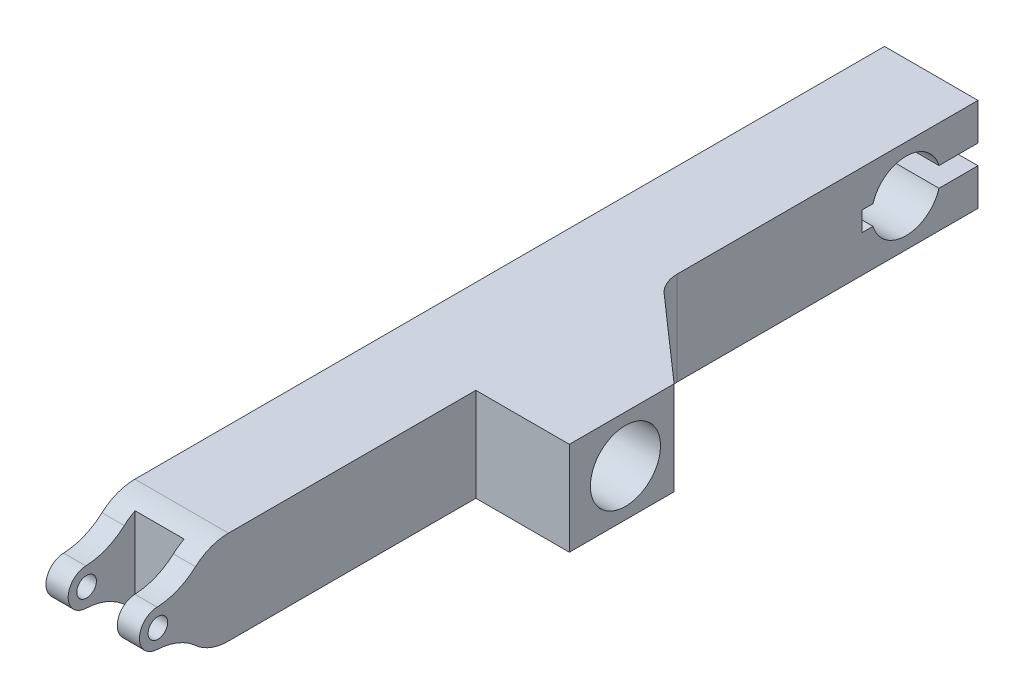
SolidWorks part; units mm, degrees
material "6061-T6 (SS)"
ref_plane "Front Plane" through (0, 0, 0) normal (0, 0, 1) x (1, 0, 0)
ref_plane "Top Plane" through (0, 0, 0) normal (0, 1, 0) x (1, 0, 0)
ref_plane "Right Plane" through (0, 0, 0) normal (1, 0, 0) x (0, 0, -1)
sketch "Sketch1" plane through (0, 0, 0) normal (1, 0, 0) x (0, 0, -1)
  line L0 (0, 0) -> (29.3372, 0) construction
  line L1 (29.3372, -19.05) -> (-175.2557, -19.05)
  line L2 (29.3372, -19.05) -> (29.3372, -4)
  line L3 (29.3372, 19.05) -> (-175.2557, 19.05)
  line L4 (-175.2557, -19.05) -> (-175.2557, 19.05)
  line L5 (-18.025, 0) -> (0, 0) construction
  line L6 (-18.025, 4) -> (-13.4425, 4)
  line L7 (-18.025, 4) -> (-18.025, -4)
  line L8 (-18.025, -4) -> (-13.4425, -4)
  line L10 (29.3372, 4) -> (29.3372, 19.05)
  line L11 (13.4425, 4) -> (29.3372, 4)
  line L12 (13.4425, -4) -> (29.3372, -4)
  line L13 (0, 0) -> (-152.4, 0) construction
  arc A0 (13.4425, 4) -> (-13.4425, 4) centre (0, 0) ccw
  arc A1 (-13.4425, -4) -> (13.4425, -4) centre (0, 0) ccw
  circle A2 centre (-152.4, 0) radius 14.2875
  point P13 (-14.025, 0)
  dimension "D1" = 28.05
  dimension "D6" = 28.575
  dimension "D2" = 8
  dimension "D3" = 4
  dimension "D4" = 38.1
  dimension "D5" = 152.4
extrude "Boss-Extrude1" add sketch "Sketch1" along normal blind 38.1
sketch "Sketch2" plane through (38.1, 0, 0) normal (1, 0, 0) x (0, 0, -1)
  line L0 (-175.2557, -19.05) -> (29.3372, -19.05) construction
  line L1 (-175.2557, 19.05) -> (-99.0557, 19.05)
  line L2 (-175.2557, 19.05) -> (-175.2557, -19.05)
  line L3 (-175.2557, -19.05) -> (-99.0557, -19.05)
  line L4 (-99.0557, 19.05) -> (-99.0557, -19.05)
  circle A0 centre (-152.4, 0) radius 14.2875 construction
  circle A1 centre (-152.4, 0) radius 14.2875
  dimension "D1" = 76.2
extrude "Boss-Extrude2" add sketch "Sketch2" along normal blind 38.1
sketch "Sketch3" plane through (0, 19.05, 0) normal (0, 1, 0) x (1, 0, 0)
  line L0 (38.1, -99.0557) -> (76.2, -132.5624)
  line L1 (76.2, -99.0557) -> (76.2, -175.2557) construction
  line L2 (38.1, -99.0557) -> (94.2773, -84.4492)
  line L3 (94.2773, -84.4492) -> (76.2, -132.5624)
extrude "Cut-Extrude1" cut sketch "Sketch3" against normal blind 38.1
fillet "Fillet1" radius 12.7 1 edges at (38.1, 0, 99.0557)
sketch "Sketch4" plane through (0, 0, 175.2557) normal (0, 0, 1) x (1, 0, 0)
  line L0 (38.1, 19.05) -> (38.1, -19.05)
  line L4 (0, 19.05) -> (0, -19.05)
  line L5 (0, -19.05) -> (76.2, -19.05)
  line L6 (76.2, -19.05) -> (76.2, 19.05)
  line L7 (76.2, 19.05) -> (0, 19.05)
  line L8 (0, 19.05) -> (0, -19.05)
  line L9 (0, -19.05) -> (38.1, -19.05)
  line L11 (38.1, 19.05) -> (0, 19.05)
  dimension "D2" = 38.1
  dimension "D3" = 38.1
  dimension "D1" = 0
extrude "Boss-Extrude3" add sketch "Sketch4" along normal blind 152.4
sketch "Sketch5" plane through (0, 0, 0) normal (-1, 0, 0) x (0, 0, 1)
  line L0 (152.4, 0) -> (304.8, 0) construction
  line L1 (0, 0) -> (152.4, 0) construction
  line L2 (327.6557, -19.05) -> (-29.3372, -19.05) construction
  line L3 (-29.3372, 19.05) -> (327.6557, 19.05) construction
  line L4 (327.6557, -19.05) -> (-29.3372, -19.05) construction
  line L5 (-29.3372, 19.05) -> (327.6557, 19.05) construction
  line L6 (292.4673, 0) -> (304.8, 0) construction
  line L7 (276.062, 19.05) -> (276.062, 26.7418)
  line L8 (276.062, 26.7418) -> (335.0382, 26.7418)
  line L9 (335.0382, 26.7418) -> (335.0382, -31.4269)
  line L10 (335.0382, -31.4269) -> (276.062, -31.4269)
  line L11 (276.062, -31.4269) -> (276.062, -19.05)
  circle A0 centre (152.4, 0) radius 14.2875 construction
  circle A1 centre (152.4, 0) radius 14.2875 construction
  circle A2 centre (304.8, 0) radius 4
  circle A3 centre (304.8, 0) radius 7.5
  arc A4 (289.4552, 13.9033) -> (305.1223, 7.4931) centre (306.1968, 32.47) ccw
  arc A5 (305.1161, -7.4933) -> (289.9026, -13.4874) centre (306.1696, -32.4711) ccw
  arc A6 (289.4552, 13.9033) -> (276.062, 19.05) centre (276.062, -0.95) ccw
  arc A7 (289.9026, -13.4874) -> (276.062, -19.05) centre (276.062, 0.95) cw
  line M15 (-29.3372, -19.05) -> (327.6557, -19.05)
  line M16 (327.6557, -19.05) -> (327.6557, 19.05)
  line M17 (327.6557, 19.05) -> (-29.3372, 19.05)
  dimension "D1" = 8
  dimension "D2" = 15
  dimension "D3" = 20
  dimension "D4" = 25
extrude "Cut-Extrude2" cut sketch "Sketch5" against normal blind 152.4 contours L11 L10 L9 L8 L7 M17 M16 M15 | A5 A7 A6 A4 A3 M15 M16 M17 | A2 region at (0, 18.4086, 301.8588) region at (0, 22.8959, 276.8903) region at (0, 0, 304.8)
sketch "Sketch6" plane through (0, -19.05, 0) normal (0, -1, 0) x (1, 0, 0)
  line L0 (19.05, 312.3) -> (19.05, 264.6122) construction
  line L1 (38.1, 312.3) -> (0, 312.3) construction
  line L7 (29.05, 339.5599) -> (9.05, 339.5599)
  line L8 (29.05, 339.5599) -> (29.05, 285.0401)
  line L9 (29.05, 285.0401) -> (9.05, 285.0401)
  line L10 (9.05, 339.5599) -> (9.05, 285.0401)
  line L11 (29.05, 339.5599) -> (9.05, 285.0401) construction
  line L12 (29.05, 285.0401) -> (9.05, 339.5599) construction
  dimension "D1" = 20
extrude "Cut-Extrude3" cut sketch "Sketch6" against normal blind 152.4
